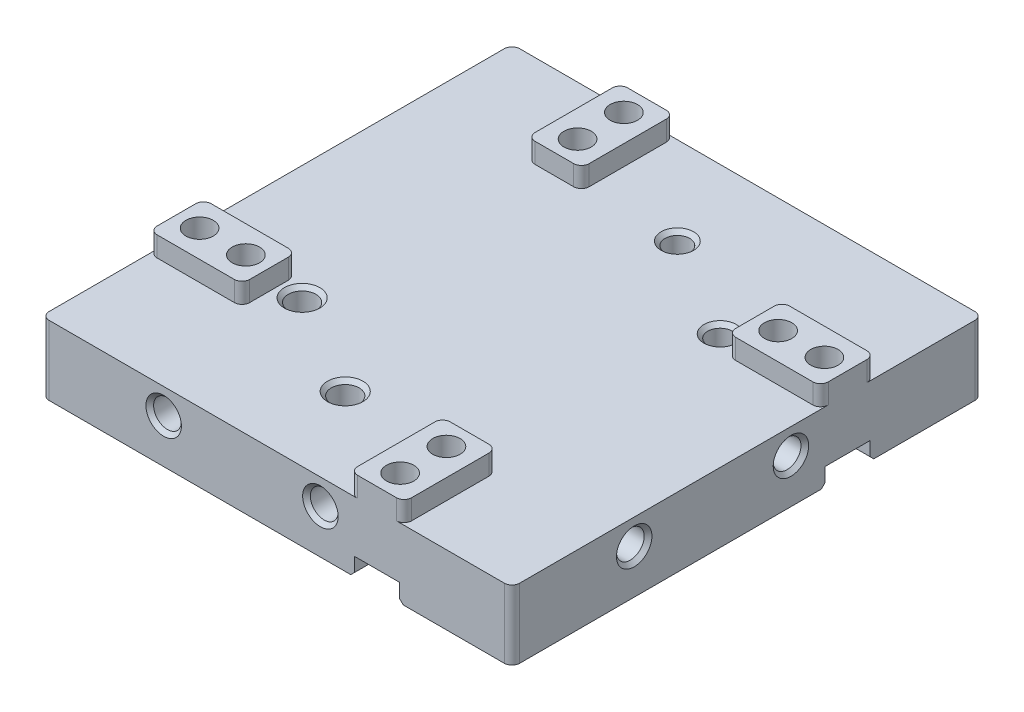
SolidWorks part; units mm, degrees
note: '?' marks a value the reader was unsure of.
ref_plane "Front Plane" through (0, 0, 0) normal (0, 0, 1) x (1, 0, 0)
ref_plane "Top Plane" through (0, 0, 0) normal (0, 1, 0) x (1, 0, 0)
ref_plane "Right Plane" through (0, 0, 0) normal (1, 0, 0) x (0, 0, -1)
sketch "Sketch1" plane through (0, 0, 0) normal (0, 1, 0) x (1, 0, 0)
  line L1 (30.5, -30.5) -> (-30.5, -30.5)
  line L2 (30.5, -30.5) -> (30.5, 30.5)
  line L3 (30.5, 30.5) -> (-30.5, 30.5)
  line L4 (-30.5, -30.5) -> (-30.5, 30.5)
  line L5 (30.5, -30.5) -> (-30.5, 30.5) construction
  line L6 (30.5, 30.5) -> (-30.5, -30.5) construction
  point P0 (0, 0)
  dimension "D1" = 61
  dimension "D2" = 61
extrude "Boss-Extrude2" add sketch "Sketch1" along normal blind 9
ref_axis "Axis1" through (0, 56.2704, 0) along (0, -1, 0)?
sketch "Sketch6" plane through (0, 9, 0) normal (0, 1, 0) x (1, 0, 0)
  line L1 (30.5, -30.5) -> (-30.5, -30.5) construction
  line L2 (30.5, -30.5) -> (30.5, 30.5) construction
  line L3 (30.5, 30.5) -> (-30.5, 30.5) construction
  line L4 (-30.5, -30.5) -> (-30.5, 30.5) construction
  line L5 (30.5, -30.5) -> (-30.5, 30.5) construction
  line L6 (30.5, 30.5) -> (-30.5, -30.5) construction
  line L7 (30.5, -30.5) -> (18.5, -30.5) construction
  line L8 (-30.5, -30.5) -> (-23.5, -30.5) construction
  line L9 (-30.5, -30.5) -> (-30.5, -18.5) construction
  line L10 (-30.5, -18.5) -> (-23.5, -18.5) construction
  line L11 (-23.5, -30.5) -> (-23.5, -18.5) construction
  line L16 (9.5, -30.5) -> (16.5, -30.5)
  line L17 (9.5, -30.5) -> (9.5, -18.5)
  line L18 (9.5, -18.5) -> (16.5, -18.5)
  line L19 (16.5, -30.5) -> (16.5, -18.5)
  line L20 (30.5, -30.5) -> (30.5, -23.5) construction
  line L21 (30.5, -23.5) -> (18.5, -23.5) construction
  line L22 (18.5, -30.5) -> (18.5, -23.5) construction
  line L23 (30.5, 16.5) -> (18.5, 16.5)
  line L24 (30.5, 16.5) -> (30.5, 9.5)
  line L25 (30.5, 9.5) -> (18.5, 9.5)
  line L26 (18.5, 16.5) -> (18.5, 9.5)
  point P0 (0, 0)
  point P17 (-27, -30.5)
  point P18 (13, -30.5)
  point P22 (30.5, 13)
  point P23 (30.5, -27)
  dimension "D1" = 61
  dimension "D2" = 61
  dimension "D3" = 12
  dimension "D4" = 7
  dimension "D5" = 40
  dimension "D6" = 12
  dimension "D7" = 7
  dimension "D8" = 7
  dimension "D9" = 12
  dimension "D10" = 40
  dimension "D11" = 12
  dimension "D12" = 7
extrude "Boss-Extrude4" add sketch "Sketch6" along normal blind 2.6
pattern_circular "CirPattern3" count 4 over 360 about axis through (0, 0, 0) along (0, 1, 0) of "Boss-Extrude4"
ref_plane "Plane1" through (0, 11.6, 0) normal (0, 1, 0) x (1, 0, 0)
sketch "Sketch8" plane through (0, 11.6, 0) normal (0, 1, 0) x (1, 0, 0)
  line L3 (16.5, -18.5) -> (9.5, -18.5) construction
  line L4 (13, -21.5) -> (13, -27.5) construction
  line L5 (16.5, -30.5) -> (16.5, -18.5) construction
  circle A2 centre (13, -21.5) radius 1.775
  circle A3 centre (13, -27.5) radius 1.775
  point P18 (13, -18.5)
  point P20 (16.5, -24.5)
  point P21 (13, -24.5)
  dimension "D3" = 3.55
  dimension "D4" = 6
extrude "Cut-Extrude3" cut sketch "Sketch8" against normal through all
pattern_circular "CirPattern4" count 4 over 360 about axis through (0, 0, 0) along (0, 1, 0) of "Cut-Extrude3"
sketch "Sketch10" plane through (0, 0, 0) normal (0, -1, 0) x (1, 0, 0)
  line L0 (-30.5, -30.5) -> (-30.5, 30.5) construction
  line L3 (-30.5, 15.9) -> (-18.6, 15.9)
  line L6 (-30.5, 15.9) -> (-30.5, 10.1)
  line L9 (-30.5, 10.1) -> (-18.6, 10.1)
  line L12 (-18.6, 15.9) -> (-18.6, 10.1)
  line L13 (-30.5, 15.9) -> (-18.6, 10.1) construction
  line L14 (-30.5, 10.1) -> (-18.6, 15.9) construction
  line L15 (15.9, 30.5) -> (15.9, 18.6)
  line L16 (15.9, 30.5) -> (10.1, 30.5)
  line L17 (10.1, 30.5) -> (10.1, 18.6)
  line L18 (15.9, 18.6) -> (10.1, 18.6)
  line L19 (15.9, 30.5) -> (10.1, 18.6) construction
  line L20 (10.1, 30.5) -> (15.9, 18.6) construction
  line L21 (30.5, -15.9) -> (18.6, -15.9)
  line L22 (30.5, -15.9) -> (30.5, -10.1)
  line L23 (30.5, -10.1) -> (18.6, -10.1)
  line L24 (18.6, -15.9) -> (18.6, -10.1)
  line L25 (30.5, -15.9) -> (18.6, -10.1) construction
  line L26 (30.5, -10.1) -> (18.6, -15.9) construction
  line L27 (-15.9, -30.5) -> (-15.9, -18.6)
  line L28 (-15.9, -30.5) -> (-10.1, -30.5)
  line L29 (-10.1, -30.5) -> (-10.1, -18.6)
  line L30 (-15.9, -18.6) -> (-10.1, -18.6)
  line L31 (-15.9, -30.5) -> (-10.1, -18.6) construction
  line L32 (-10.1, -30.5) -> (-15.9, -18.6) construction
  circle A8 centre (-21.5, 13) radius 2.9 construction
  circle A9 centre (13, 21.5) radius 2.9 construction
  circle A10 centre (21.5, -13) radius 2.9 construction
  circle A11 centre (-13, -21.5) radius 2.9 construction
  point P8 (-24.55, 13)
  point P18 (13, 24.55)
  point P25 (24.55, -13)
  point P32 (-13, -24.55)
  point P33 (0, 0)
  dimension "D1" = 5.8
  dimension "D2" = 4
extrude "Cut-Extrude6" cut sketch "Sketch10" against normal blind 2.3
sketch "Sketch12" plane through (0, 0, 0) normal (0, -1, 0) x (1, 0, 0)
  line L1 (26, -26) -> (-26, -26) construction
  line L2 (26, -26) -> (26, 26) construction
  line L3 (26, 26) -> (-26, 26) construction
  line L4 (-26, -26) -> (-26, 26) construction
  line L5 (26, -26) -> (-26, 26) construction
  line L6 (26, 26) -> (-26, -26) construction
  circle A0 centre (-26, 26) radius 2.05
  circle A1 centre (26, 26) radius 2.05
  circle A2 centre (-26, -26) radius 2.05
  circle A3 centre (26, -26) radius 2.05
  point P0 (0, 0)
  dimension "D3" = 4.1
  dimension "D1" = 52
  dimension "D2" = 52
extrude "Cut-Extrude8" cut sketch "Sketch12" against normal blind 6.5 contours A1 | A3 | A2 | A0
fillet "Fillet1" radius 1 20 edges at (30.5, 10.3, -9.5) (30.5, 10.3, -16.5) (18.5, 10.3, -16.5) (18.5, 10.3, -9.5) (9.5, 10.3, 18.5) (9.5, 10.3, 30.5) (16.5, 10.3, 30.5) (16.5, 10.3, 18.5) (-18.5, 10.3, 9.5) (-30.5, 10.3, 9.5) (-30.5, 10.3, 16.5) (-18.5, 10.3, 16.5) (-9.5, 10.3, -18.5) (-9.5, 10.3, -30.5) (-16.5, 10.3, -30.5) (-16.5, 10.3, -18.5) (-30.5, 4.5, -30.5) (30.5, 4.5, -30.5) (30.5, 4.5, 30.5) (-30.5, 4.5, 30.5)
sketch "Sketch14" plane through (0, 0, 30.5) normal (0, 0, 1) x (1, 0, 0)
  line L1 (-14.66, 5.71) -> (5.66, 5.71) construction
  line L3 (-30.5, 0) -> (-30.5, 9) construction
  line L4 (-29.5, 9) -> (10.5, 9) construction
  circle A0 centre (-14.66, 5.71) radius 1.8
  circle A1 centre (5.66, 5.71) radius 1.8
  point P2 (-4.5, 5.71)
  dimension "D1" = 3.6
  dimension "D4" = 3.29
  dimension "D2" = 26
  dimension "D3" = 20.32
extrude "Cut-Extrude10" cut sketch "Sketch14" against normal blind 6.5
pattern_circular "CirPattern5" count 4 over 360 about axis through (0, 0, 0) along (0, 1, 0) of "Cut-Extrude10"
chamfer "Chamfer1" distance 0.5 angle 45 24 edges at (-26, 0, -28.05) (26, 0, -28.05) (26, 0, 23.95) (-26, 0, 23.95) (-24.55, 0, 15.9) (-18.6, 0, 13) (-24.55, 0, 10.1) (15.9, 0, 24.55) (10.1, 0, 24.55) (13, 0, 18.6) (24.55, 0, -10.1) (18.6, 0, -13) (24.55, 0, -15.9) (-15.9, 0, -24.55) (-10.1, 0, -24.55) (-13, 0, -18.6) (-7.46, 5.71, -30.5) (12.86, 5.71, -30.5) (30.5, 5.71, -7.46) (30.5, 5.71, 12.86) (7.46, 5.71, 30.5) (-12.86, 5.71, 30.5) (-30.5, 5.71, 7.46) (-30.5, 5.71, -12.86)
sketch "Sketch16" plane through (0, 9, 0) normal (0, 1, 0) x (1, 0, 0)
  line L0 (15.5, 11.4784) -> (-2.3353, -19.2852) construction
  line L1 (15.5, 11.4784) -> (2.3155, 19.1221) construction
  line L2 (2.3155, 19.1221) -> (-15.6322, -11.5763) construction
  line L3 (-2.3353, -19.2852) -> (-15.6322, -11.5763) construction
  line L4 (15.5, 11.4784) -> (-15.6322, -11.5763) construction
  line L5 (2.3155, 19.1221) -> (-2.3353, -19.2852) construction
  line L6 (8.9078, 15.3003) -> (-8.9837, -15.4308) construction
  line L7 (18.5, 15.5) -> (18.5, 10.5) construction
  circle A0 centre (-15.6322, -11.5763) radius 1.8
  circle A1 centre (2.3155, 19.1221) radius 1.6
  circle A2 centre (-2.3353, -19.2852) radius 1.8
  circle A3 centre (15.5, 11.4784) radius 1.6
  point P0 (0, 0)
  point P15 (-8.9837, -15.4308)
  dimension "D3" = 3.6
  dimension "D4" = 3.2
  dimension "D1" = 35.56
  dimension "D2" = 15.24
  dimension "D5" = 0
  dimension "D6" = 3
  dimension "D7" = 15.37
extrude "Cut-Extrude11" cut sketch "Sketch16" against normal blind 6.5 contours A0 | A2
sketch "Sketch18" plane through (0, 9, 0) normal (0, 1, 0) x (1, 0, 0)
  circle A1 centre (15.5, 11.4784) radius 1.6
  circle A2 centre (15.5, 11.4784) radius 1.6
  circle A3 centre (-2.3353, -19.2852) radius 1.8
  circle A4 centre (-2.3353, -19.2852) radius 1.8 construction
  circle A5 centre (2.3155, 19.1221) radius 1.6
  circle A6 centre (2.3155, 19.1221) radius 1.6
  circle A7 centre (-15.6322, -11.5763) radius 1.8
  circle A8 centre (-15.6322, -11.5763) radius 1.8 construction
  dimension "D1" = 0
  dimension "D2" = 0
  dimension "D3" = 0
  dimension "D4" = 0
extrude "Cut-Extrude12" cut sketch "Sketch18" against normal blind 4.5
chamfer "Chamfer2" distance 0.5 angle 45 4 edges at (-2.3353, 9, 21.0852) (-15.6322, 9, 13.3763) (15.5, 9, -9.8784) (2.3155, 9, -17.5221)
equation "\"D6@Sketch6\"=\"D3@Sketch6\""
equation "\"D7@Sketch6\"=\"D4@Sketch6\""
equation "\"D8@Sketch6\"=\"D4@Sketch6\""
equation "\"D9@Sketch6\"=\"D3@Sketch6\""
equation "\"D10@Sketch6\"=\"D5@Sketch6\""
equation "\"D11@Sketch6\"=\"D3@Sketch6\""
equation "\"D12@Sketch6\"=\"D4@Sketch6\""
